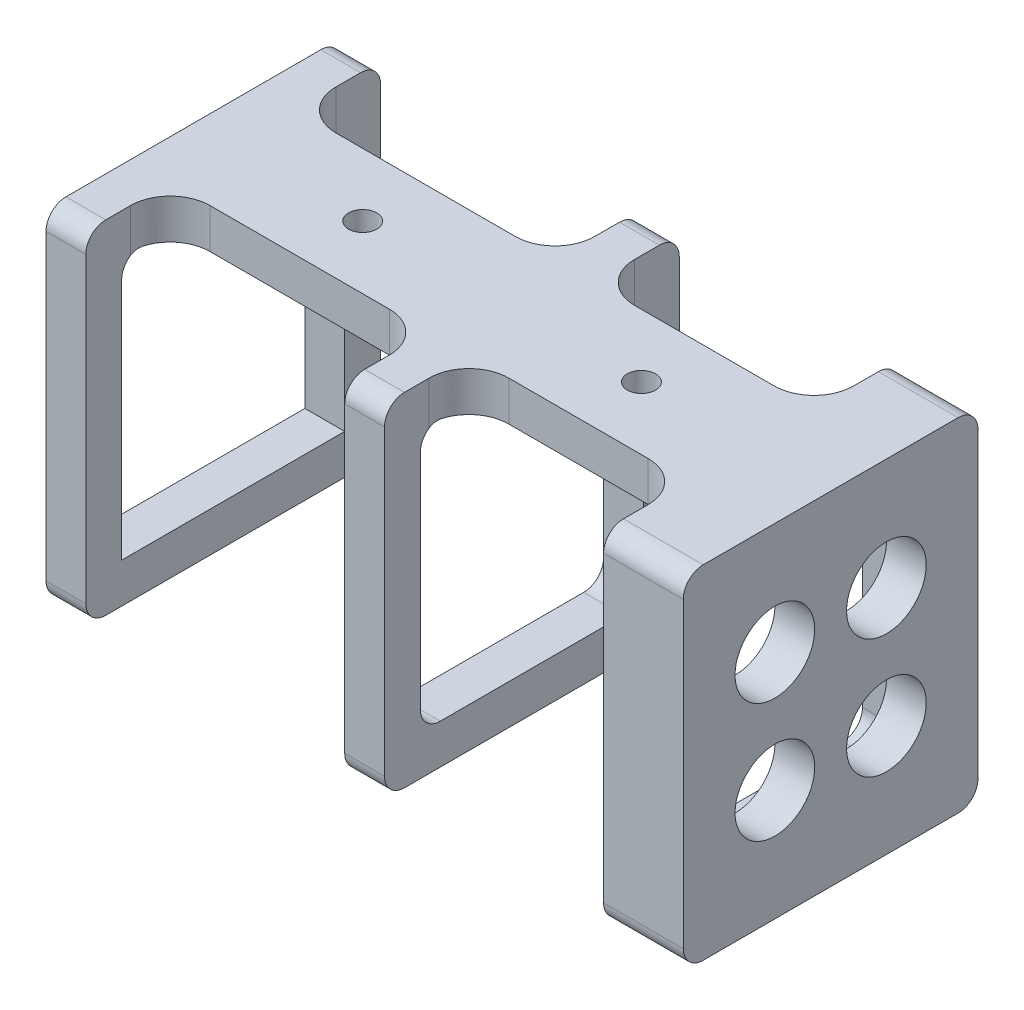
SolidWorks part; units mm, degrees
ref_plane "Front" through (0, 0, 0) normal (0, 0, 1) x (1, 0, 0)
ref_plane "Top" through (0, 0, 0) normal (0, 1, 0) x (1, 0, 0)
ref_plane "Right" through (0, 0, 0) normal (1, 0, 0) x (0, 0, -1)
sketch "Sketch1" plane through (0, 0, 0) normal (0, 1, 0) x (1, 0, 0)
  line L1 (-50.8, -10.033) -> (50.8, -10.033)
  line L2 (-50.8, -10.033) -> (-50.8, 10.033)
  line L3 (-50.8, 10.033) -> (50.8, 10.033)
  line L4 (50.8, -10.033) -> (50.8, 10.033)
  line L5 (-50.8, -10.033) -> (50.8, 10.033) construction
  line L6 (-50.8, 10.033) -> (50.8, -10.033) construction
  point P0 (0, 0)
  dimension "D1" = 101.6
  dimension "D2" = 20.066
extrude "Boss-Extrude1" add sketch "Sketch1" along normal blind 6.35
sketch "Sketch2" plane through (0, 6.35, 0) normal (0, 1, 0) x (1, 0, 0)
  line L0 (0, 0) -> (50000, 0) construction
  line L1 (50.8, -10.033) -> (50.8, 10.033) construction
  line L2 (44.45, -23.495) -> (50.8, -23.495)
  line L3 (44.45, -23.495) -> (44.45, 23.495)
  line L4 (44.45, 23.495) -> (50.8, 23.495)
  line L5 (50.8, -23.495) -> (50.8, 23.495)
  line L6 (44.45, -23.495) -> (50.8, 23.495) construction
  line L7 (44.45, 23.495) -> (50.8, -23.495) construction
  line L8 (-50.8, 10.033) -> (-50.8, -10.033) construction
  line L9 (-44.45, -23.495) -> (-50.8, -23.495)
  line L10 (-44.45, -23.495) -> (-44.45, 23.495)
  line L11 (-44.45, 23.495) -> (-50.8, 23.495)
  line L12 (-50.8, -23.495) -> (-50.8, 23.495)
  line L13 (-44.45, -23.495) -> (-50.8, 23.495) construction
  line L14 (-44.45, 23.495) -> (-50.8, -23.495) construction
  line L16 (-3.175, 23.495) -> (3.175, 23.495)
  line L17 (-3.175, 23.495) -> (-3.175, -23.495)
  line L18 (-3.175, -23.495) -> (3.175, -23.495)
  line L19 (3.175, 23.495) -> (3.175, -23.495)
  line L20 (-3.175, 23.495) -> (3.175, -23.495) construction
  line L21 (-3.175, -23.495) -> (3.175, 23.495) construction
  point P3 (47.625, 0)
  point P10 (-47.625, 0)
  point P17 (0, 0)
  dimension "D1" = 6.35
  dimension "D2" = 46.99
extrude "Boss-Extrude2" add sketch "Sketch2" against normal blind 54.61
sketch "Sketch3" plane through (3.175, 0, 0) normal (1, 0, 0) x (0, 0, -1)
  line L0 (0, 0) -> (0, -48.26) construction
  line L1 (-23.495, -48.26) -> (23.495, -48.26) construction
  line L2 (10.033, 0) -> (-10.033, 0) construction
  line L3 (17.78, -41.91) -> (-17.78, -41.91)
  line L4 (17.78, -41.91) -> (17.78, 0)
  line L5 (17.78, 0) -> (-17.78, 0)
  line L6 (-17.78, -41.91) -> (-17.78, 0)
  line L7 (17.78, -41.91) -> (-17.78, 0) construction
  line L8 (17.78, 0) -> (-17.78, -41.91) construction
  point P5 (0, -20.955)
  dimension "D1" = 35.56
  dimension "D2" = 41.91
extrude "Cut-Extrude1" cut sketch "Sketch3" against normal through all
sketch "Sketch4" plane through (44.45, 0, 0) normal (-1, 0, 0) x (0, 0, 1)
  line L12 (10.033, 0) -> (17.78, 0)
  line L13 (10.033, 6.35) -> (10.033, 0)
  line L14 (23.495, 6.35) -> (10.033, 6.35)
  line L15 (23.495, -48.26) -> (23.495, 6.35)
  line L16 (-23.495, -48.26) -> (23.495, -48.26)
  line L17 (-23.495, 6.35) -> (-23.495, -48.26)
  line L18 (-10.033, 6.35) -> (-23.495, 6.35)
  line L19 (-10.033, 0) -> (-10.033, 6.35)
  line L20 (-17.78, 0) -> (-10.033, 0)
  line L21 (-17.78, -41.91) -> (-17.78, 0)
  line L22 (17.78, -41.91) -> (-17.78, -41.91)
  line L23 (17.78, 0) -> (17.78, -41.91)
  line L24 (10.033, 0) -> (17.78, 0)
  line L25 (10.033, 6.35) -> (10.033, 0)
  line L26 (23.495, 6.35) -> (10.033, 6.35)
  line L27 (23.495, -48.26) -> (23.495, 6.35)
  line L28 (-23.495, -48.26) -> (23.495, -48.26)
  line L29 (-23.495, 6.35) -> (-23.495, -48.26)
  line L30 (-10.033, 6.35) -> (-23.495, 6.35)
  line L31 (-10.033, 0) -> (-10.033, 6.35)
  line L32 (-17.78, 0) -> (-10.033, 0)
  line L33 (-17.78, -41.91) -> (-17.78, 0)
  line L34 (17.78, -41.91) -> (-17.78, -41.91)
  line L35 (17.78, 0) -> (17.78, -41.91)
  dimension "D1" = 0
extrude "Boss-Extrude3" add sketch "Sketch4" along normal blind 6.35
sketch "Sketch5" plane through (44.45, 0, 0) normal (-1, 0, 0) x (0, 0, 1)
  line L0 (-8.89, 0) -> (-8.89, -41.91) construction
  line L1 (17.78, 0) -> (-17.78, 0) construction
  line L2 (17.78, -41.91) -> (-17.78, -41.91) construction
  line L3 (8.89, 0) -> (8.89, -41.91) construction
  line L4 (17.78, 0) -> (17.78, -41.91) construction
  line L5 (-17.78, -41.91) -> (-17.78, 0) construction
  line L7 (-8.89, -30.48) -> (8.89, -30.48) construction
  line L8 (-8.89, -30.48) -> (-8.89, -11.43) construction
  line L9 (-8.89, -11.43) -> (8.89, -11.43) construction
  line L10 (8.89, -30.48) -> (8.89, -11.43) construction
  circle A0 centre (-8.89, -11.43) radius 6.35
  circle A1 centre (-8.89, -30.48) radius 6.35
  circle A2 centre (8.89, -30.48) radius 6.35
  circle A3 centre (8.89, -11.43) radius 6.35
  point P22 (0, -11.43)
  dimension "D5" = 12.7
  dimension "D1" = 8.89
  dimension "D2" = 8.89
  dimension "D3" = 19.05
  dimension "D4" = 11.43
extrude "Cut-Extrude2" cut sketch "Sketch5" against normal through all
sketch "Sketch6" plane through (0, 0, 0) normal (0, -1, 0) x (1, 0, 0)
  line L0 (-23.8125, -10.033) -> (-23.8125, 10.033) construction
  line L1 (-3.175, -10.033) -> (-44.45, -10.033) construction
  line L2 (-44.45, 10.033) -> (-3.175, 10.033) construction
  line L3 (20.6375, -10.033) -> (20.6375, 10.033) construction
  line L4 (38.1, -10.033) -> (3.175, -10.033) construction
  line L5 (3.175, 10.033) -> (38.1, 10.033) construction
  circle A0 centre (-23.8125, 0) radius 2.25
  circle A1 centre (20.6375, 0) radius 2.25
  dimension "D1" = 4.5
extrude "Cut-Extrude3" cut sketch "Sketch6" against normal through all
fillet "Fillet1" radius 3.175 22 edges at (-47.625, 0, -17.78) (-47.625, 0, 17.78) (0, 0, -17.78) (41.275, 0, -17.78) (41.275, 0, 17.78) (0, 0, 17.78) (0, -41.91, -17.78) (0, -41.91, 17.78) (41.275, -41.91, 17.78) (41.275, -41.91, -17.78) (44.45, -48.26, -23.495) (0, -48.26, -23.495) (-47.625, -48.26, -23.495) (-47.625, -48.26, 23.495) (0, -48.26, 23.495) (44.45, -48.26, 23.495) (44.45, 6.35, 23.495) (-47.625, 6.35, 23.495) (44.45, 6.35, -23.495) (-47.625, 6.35, -23.495) (0, 6.35, -23.495) (0, 6.35, 23.495)
fillet "Fillet2" radius 6.35 8 edges at (38.1, 3.175, -10.033) (38.1, 3.175, 10.033) (-44.45, 3.175, -10.033) (3.175, 3.175, -10.033) (-3.175, 3.175, -10.033) (-44.45, 3.175, 10.033) (3.175, 3.175, 10.033) (-3.175, 3.175, 10.033)
